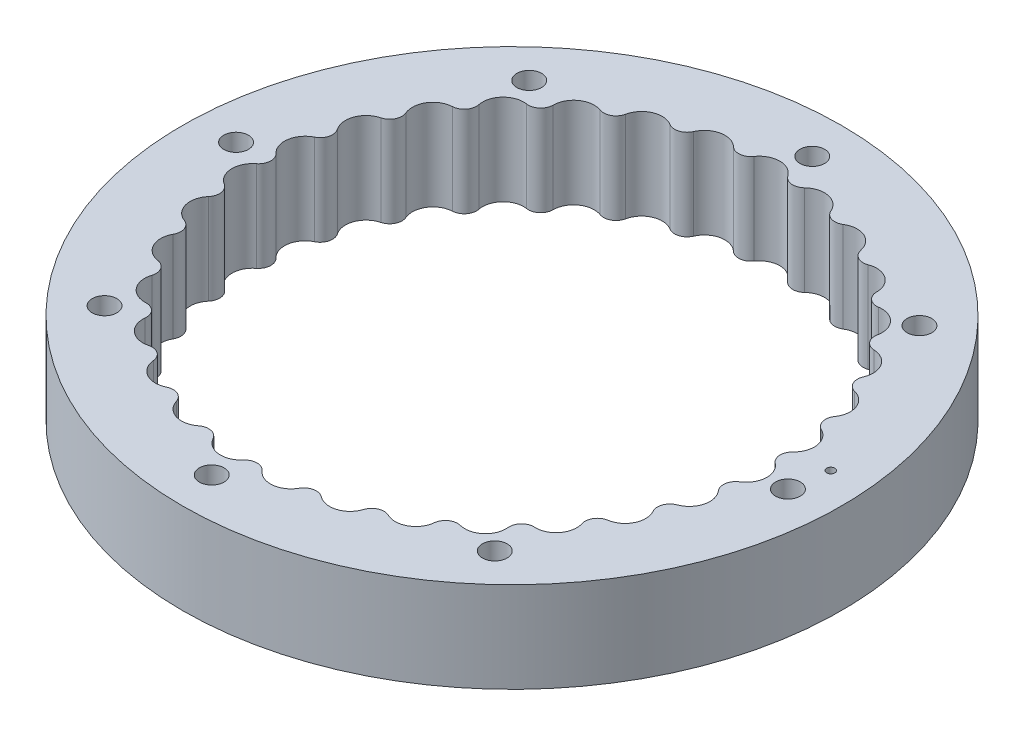
SolidWorks part; units mm, degrees
ref_plane "Front Plane" through (0, 0, 0) normal (0, 0, 1) x (1, 0, 0)
ref_plane "Top Plane" through (0, 0, 0) normal (0, 1, 0) x (1, 0, 0)
ref_plane "Right Plane" through (0, 0, 0) normal (1, 0, 0) x (0, 0, -1)
sketch "Sketch1" plane through (0, 0, 0) normal (0, 1, 0) x (1, 0, 0)
  arc A0 (-38.2573, 46.221) -> (-39.8947, 44.8153) centre (0, 0) ccw
  arc A1 (4.9957, 59.7917) -> (-4.9957, 59.7917) centre (0, 60) ccw
  arc A2 (16.9294, 57.5621) -> (7.1426, 59.5733) centre (12.0779, 58.7718) ccw
  arc A3 (28.17, 52.976) -> (18.9884, 56.9161) centre (23.6614, 55.1375) ccw
  arc A4 (38.2573, 46.221) -> (30.0568, 51.9287) centre (34.2761, 49.2458) ccw
  arc A5 (46.7784, 37.5737) -> (39.8947, 44.8153) centre (43.4876, 41.338) ccw
  arc A6 (53.3844, 27.3881) -> (48.0993, 35.8672) centre (50.9187, 31.7378) ccw
  arc A7 (57.8048, 16.0813) -> (54.3347, 25.4506) centre (56.2651, 20.8383) ccw
  arc A8 (59.8586, 4.1161) -> (58.3457, 13.9922) centre (59.3081, 9.0857) ccw
  arc A9 (59.4619, -8.0176) -> (59.968, 1.9608) centre (59.923, -3.039) ccw
  arc A10 (56.6308, -19.8231) -> (59.1351, -10.1508) centre (58.0846, -15.0392) ccw
  arc A11 (51.4812, -30.817) -> (55.8813, -21.8468) centre (53.8683, -26.4236) ccw
  arc A12 (44.2239, -40.5493) -> (50.3397, -32.6484) centre (47.4465, -36.7264) ccw
  arc A13 (35.1562, -48.6214) -> (42.7371, -42.1134) centre (39.0823, -45.5255) ccw
  arc A14 (24.6491, -54.703) -> (33.3849, -49.8542) centre (29.1181, -52.4608) ccw
  arc A15 (13.1329, -58.5451) -> (22.666, -55.5541) centre (17.9618, -57.2484) ccw
  arc A16 (1.079, -59.9903) -> (11.019, -58.9795) centre (6.0701, -59.6922) ccw
  arc A17 (-11.019, -58.9795) -> (-1.079, -59.9903) centre (-6.0701, -59.6922) ccw
  arc A18 (-22.666, -55.5541) -> (-13.1329, -58.5451) centre (-17.9618, -57.2484) ccw
  arc A19 (-33.3849, -49.8542) -> (-24.6491, -54.703) centre (-29.1181, -52.4608) ccw
  arc A20 (-42.7371, -42.1134) -> (-35.1562, -48.6214) centre (-39.0823, -45.5255) ccw
  arc A21 (-50.3397, -32.6484) -> (-44.2239, -40.5493) centre (-47.4465, -36.7264) ccw
  arc A22 (-55.8813, -21.8468) -> (-51.4812, -30.817) centre (-53.8683, -26.4236) ccw
  arc A23 (-59.1351, -10.1508) -> (-56.6308, -19.8231) centre (-58.0846, -15.0392) ccw
  arc A24 (-59.968, 1.9608) -> (-59.4619, -8.0176) centre (-59.923, -3.039) ccw
  arc A25 (-58.3457, 13.9922) -> (-59.8586, 4.1161) centre (-59.3081, 9.0857) ccw
  arc A26 (-54.3347, 25.4506) -> (-57.8048, 16.0813) centre (-56.2651, 20.8383) ccw
  arc A27 (-48.0993, 35.8672) -> (-53.3844, 27.3881) centre (-50.9187, 31.7378) ccw
  arc A28 (-39.8947, 44.8153) -> (-46.7784, 37.5737) centre (-43.4876, 41.338) ccw
  arc A29 (-30.0568, 51.9287) -> (-38.2573, 46.221) centre (-34.2761, 49.2458) ccw
  arc A30 (-18.9884, 56.9161) -> (-28.17, 52.976) centre (-23.6614, 55.1375) ccw
  arc A31 (-7.1426, 59.5733) -> (-16.9294, 57.5621) centre (-12.0779, 58.7718) ccw
  circle A32 centre (0, 0) radius 80
  arc A33 (-46.7784, 37.5737) -> (-48.0993, 35.8672) centre (0, 0) ccw
  arc A34 (-53.3844, 27.3881) -> (-54.3347, 25.4506) centre (0, 0) ccw
  arc A35 (-57.8048, 16.0813) -> (-58.3457, 13.9922) centre (0, 0) ccw
  arc A36 (-59.8586, 4.1161) -> (-59.968, 1.9608) centre (0, 0) ccw
  arc A37 (-59.4619, -8.0176) -> (-59.1351, -10.1508) centre (0, 0) ccw
  arc A38 (-56.6308, -19.8231) -> (-55.8813, -21.8468) centre (0, 0) ccw
  arc A39 (-51.4812, -30.817) -> (-50.3397, -32.6484) centre (0, 0) ccw
  arc A40 (-44.2239, -40.5493) -> (-42.7371, -42.1134) centre (0, 0) ccw
  arc A41 (-35.1562, -48.6214) -> (-33.3849, -49.8542) centre (0, 0) ccw
  arc A42 (-24.6491, -54.703) -> (-22.666, -55.5541) centre (0, 0) ccw
  arc A43 (-13.1329, -58.5451) -> (-11.019, -58.9795) centre (0, 0) ccw
  arc A44 (11.019, -58.9795) -> (13.1329, -58.5451) centre (0, 0) ccw
  arc A45 (-1.079, -59.9903) -> (1.079, -59.9903) centre (0, 0) ccw
  arc A46 (22.666, -55.5541) -> (24.6491, -54.703) centre (0, 0) ccw
  arc A47 (33.3849, -49.8542) -> (35.1562, -48.6214) centre (0, 0) ccw
  arc A48 (42.7371, -42.1134) -> (44.2239, -40.5493) centre (0, 0) ccw
  arc A49 (50.3397, -32.6484) -> (51.4812, -30.817) centre (0, 0) ccw
  arc A50 (55.8813, -21.8468) -> (56.6308, -19.8231) centre (0, 0) ccw
  arc A51 (59.1351, -10.1508) -> (59.4619, -8.0176) centre (0, 0) ccw
  arc A52 (59.968, 1.9608) -> (59.8586, 4.1161) centre (0, 0) ccw
  arc A53 (58.3457, 13.9922) -> (57.8048, 16.0813) centre (0, 0) ccw
  arc A54 (54.3347, 25.4506) -> (53.3844, 27.3881) centre (0, 0) ccw
  arc A55 (48.0993, 35.8672) -> (46.7784, 37.5737) centre (0, 0) ccw
  arc A56 (39.8947, 44.8153) -> (38.2573, 46.221) centre (0, 0) ccw
  arc A57 (30.0568, 51.9287) -> (28.17, 52.976) centre (0, 0) ccw
  arc A58 (18.9884, 56.9161) -> (16.9294, 57.5621) centre (0, 0) ccw
  arc A59 (7.1426, 59.5733) -> (4.9957, 59.7917) centre (0, 0) ccw
  arc A60 (-4.9957, 59.7917) -> (-7.1426, 59.5733) centre (0, 0) ccw
  arc A61 (-16.9294, 57.5621) -> (-18.9884, 56.9161) centre (0, 0) ccw
  arc A62 (-28.17, 52.976) -> (-30.0568, 51.9287) centre (0, 0) ccw
  dimension "D1" = 120
  dimension "D2" = 10
  dimension "D4" = 160
  dimension "D3" = 31
extrude "Boss-Extrude1" add sketch "Sketch1" along normal blind 22
fillet "Fillet1" radius 2.5 62 edges at (44.2239, 11, 40.5493) (42.7371, 11, 42.1134) (35.1562, 11, 48.6214) (33.3849, 11, 49.8542) (24.6491, 11, 54.703) (22.666, 11, 55.5541) (13.1329, 11, 58.5451) (11.019, 11, 58.9795) (1.079, 11, 59.9903) (-1.079, 11, 59.9903) (-11.019, 11, 58.9795) (-13.1329, 11, 58.5451) (-22.666, 11, 55.5541) (-24.6491, 11, 54.703) (-33.3849, 11, 49.8542) (-35.1562, 11, 48.6214) (-42.7371, 11, 42.1134) (-44.2239, 11, 40.5493) (-50.3397, 11, 32.6484) (-51.4812, 11, 30.817) (-55.8813, 11, 21.8468) (-56.6308, 11, 19.8231) (-59.1351, 11, 10.1508) (-59.4619, 11, 8.0176) (-59.968, 11, -1.9608) (-59.8586, 11, -4.1161) (-58.3457, 11, -13.9922) (-57.8048, 11, -16.0813) (-54.3347, 11, -25.4506) (-53.3844, 11, -27.3881) (50.3397, 11, 32.6484) (51.4812, 11, 30.817) (55.8813, 11, 21.8468) (56.6308, 11, 19.8231) (59.1351, 11, 10.1508) (59.4619, 11, 8.0176) (59.968, 11, -1.9608) (59.8586, 11, -4.1161) (58.3457, 11, -13.9922) (57.8048, 11, -16.0813) (54.3347, 11, -25.4506) (53.3844, 11, -27.3881) (48.0993, 11, -35.8672) (46.7784, 11, -37.5737) (38.2573, 11, -46.221) (39.8947, 11, -44.8153) (30.0568, 11, -51.9287) (28.17, 11, -52.976) (18.9884, 11, -56.9161) (16.9294, 11, -57.5621) (7.1426, 11, -59.5733) (4.9957, 11, -59.7917) (-4.9957, 11, -59.7917) (-7.1426, 11, -59.5733) (-16.9294, 11, -57.5621) (-18.9884, 11, -56.9161) (-28.17, 11, -52.976) (-30.0568, 11, -51.9287) (-38.2573, 11, -46.221) (-39.8947, 11, -44.8153) (-46.7784, 11, -37.5737) (-48.0993, 11, -35.8672)
fillet "Fillet2" radius 3 31 edges at (60.0791, 11, -3.0469) (59.4626, 11, 9.1093) (56.4117, 11, 20.8926) (51.0513, 11, 31.8205) (43.6009, 11, 41.4457) (34.3654, 11, 49.3741) (23.723, 11, 55.2812) (12.1094, 11, 58.9249) (0, 11, 60.1564) (-12.1094, 11, 58.9249) (-23.723, 11, 55.2812) (-34.3654, 11, 49.3741) (-43.6009, 11, 41.4457) (-51.0513, 11, 31.8205) (-56.4117, 11, 20.8926) (-59.4626, 11, 9.1093) (-60.0791, 11, -3.0469) (-58.236, 11, -15.0783) (-54.0086, 11, -26.4925) (58.236, 11, -15.0783) (54.0086, 11, -26.4925) (47.5702, 11, -36.8221) (39.1842, 11, -45.6441) (29.194, 11, -52.5975) (18.0086, 11, -57.3975) (6.0859, 11, -59.8477) (-6.0859, 11, -59.8477) (-18.0086, 11, -57.3975) (-29.194, 11, -52.5975) (-39.1842, 11, -45.6441) (-47.5702, 11, -36.8221)
sketch "Sketch3" plane through (0, 22, 0) normal (0, 1, 0) x (1, 0, 0)
  circle A0 centre (0, 0) radius 70 construction
  circle A1 centre (69.9376, -2.9549) radius 3
  circle A2 centre (47.3639, -51.5428) radius 3
  circle A3 centre (-2.9549, -69.9376) radius 3
  circle A4 centre (-51.5428, -47.3639) radius 3
  circle A5 centre (-69.9376, 2.9549) radius 3
  circle A6 centre (-47.3639, 51.5428) radius 3
  circle A7 centre (2.9549, 69.9376) radius 3
  circle A8 centre (51.5428, 47.3639) radius 3
  point P17 (0, 0)
  point P20 (69.9376, -2.9549)
  dimension "D1" = 140
  dimension "D2" = 6
  dimension "D4" = 2.9549
  dimension "D3" = 8
extrude "Cut-Extrude1" cut sketch "Sketch3" against normal through all
sketch "Sketch4" plane through (0, 0, 0) normal (0, -1, 0) x (1, 0, 0)
  circle A0 centre (66.1432, 27.1816) radius 1
  dimension "D1" = 2
sketch "Sketch5" plane through (0, 22, 0) normal (0, 1, 0) x (1, 0, 0)
  circle A0 centre (71.247, 6.1342) radius 1
  dimension "D1" = 2
extrude "Cut-Extrude3" cut sketch "Sketch5" against normal blind 2
equation "\"R_ROLL\"= 5mm"
equation "\"D_SUN\"= 120mm"
equation "\"NUM_ROLL\"= 31"
equation "\"RHO\"= 1mm"
equation "\"D_SHAFT\"= 20mm"
equation "\"D_OUTPUT\"= 80mm"
equation "\"NUM_OUT\"= 8"
equation "\"R_OUT_ROLL\"= 5mm"
equation "\"D1@Sketch1\"=\"D_SUN\""
equation "\"D2@Sketch1\"=\"R_ROLL\"*2"
equation "\"D3@Sketch1\"=\"NUM_ROLL\""
equation "\"a\"= \"D_SUN\" + 30"
equation "\"D4@Sketch1\"=\"D_SUN\"+40"
